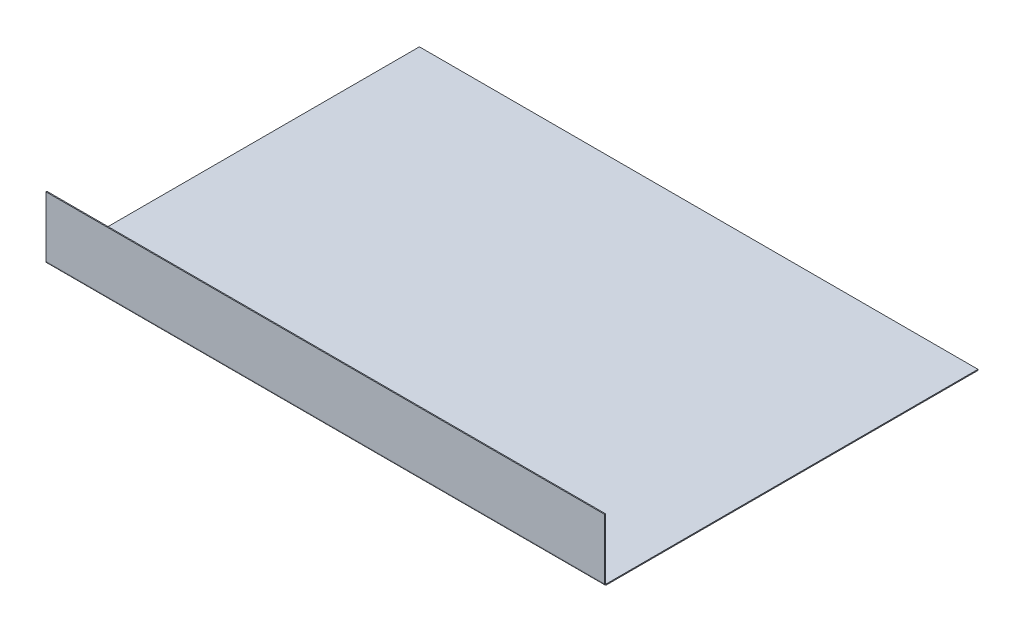
SolidWorks part; units mm, degrees
note: The reader was unsure of these and kept them because the rebuilt part matched: flange length of "Edge-Flange1".
ref_plane "Front Plane" through (0, 0, 0) normal (0, 0, 1) x (1, 0, 0)
ref_plane "Top Plane" through (0, 0, 0) normal (0, 1, 0) x (1, 0, 0)
ref_plane "Right Plane" through (0, 0, 0) normal (1, 0, 0) x (0, 0, -1)
sketch "Sketch1" plane through (0, 0, 0) normal (0, 1, 0) x (1, 0, 0)
  line L1 (-228.6, 0) -> (228.6, 0)
  line L2 (-228.6, 0) -> (-228.6, -304.8)
  line L3 (-228.6, -304.8) -> (228.6, -304.8)
  line L4 (228.6, 0) -> (228.6, -304.8)
  dimension "D1" = 457.2
  dimension "D2" = 304.8
base flange "Base-Flange1" sketch "Sketch1" thickness 0.8128 reverse thickness direction no parameters "D1"=0.7366
edge flange "Edge-Flange1" sketch "Sketch8" flange angle 90 flange length 50.8 flange position material outside bend radius 0.7366 thickness 0.8128 relief rectangular parameters "D6"=10
sketch "Sketch8" plane through (0, 0, 304.8) normal (0, 0, 1) x (1, 0, 0)
  line L0 (-228.6, 0) -> (228.6, 0) construction
  line L1 (-228.6, 0) -> (228.6, 0)
  line L2 (-228.6, 0) -> (-228.6, 49.9872)
  line L3 (-228.6, 49.9872) -> (228.6, 49.9872)
  line L4 (228.6, 49.9872) -> (228.6, 0)
bend "EdgeBend1" bend radius 0.7366 bend angle 90 parameters "D5"=1
sketch "Bend-Lines1" plane through (0, 0, 0) normal (0, 1, 0) x (1, 0, 0)
sketch "Bounding-Box1" plane through (0, 0, 0) normal (0, 1, 0) x (1, 0, 0)
sheet metal parameters "Sheet-Metal1" thickness 0.8128 parameters "D1"=0.7366
flat pattern "Flat-Pattern1" [suppressed]
sketch "Bend-Lines2" plane through (0, 0, 0) normal (0, 1, 0) x (1, 0, 0)
sketch "Bounding-Box2" [suppressed] plane through (0, 0, 0) normal (0, 1, 0) x (1, 0, 0)
sheet metal parameters "Sheet-Metal2" thickness 0.8128 parameters "D1"=0.7366
flat pattern "Flat-Pattern1" [suppressed]
sketch "Bend-Lines2" plane through (0, 0, 0) normal (0, 1, 0) x (1, 0, 0)
sketch "Bounding-Box2" [suppressed] plane through (0, 0, 0) normal (0, 1, 0) x (1, 0, 0)
bend of the flat pattern "Flatten-<EdgeBend1>1"
